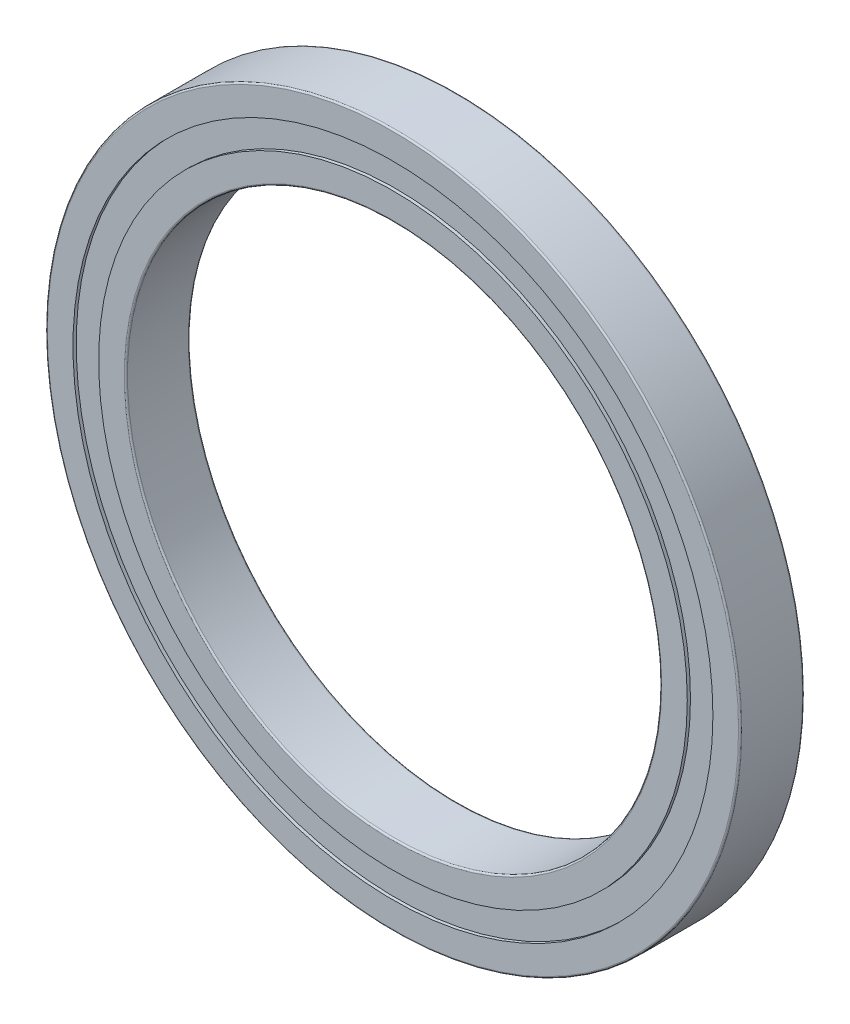
SolidWorks part; units mm, degrees
ref_plane "Front Plane" through (0, 0, 0) normal (0, 0, 1) x (1, 0, 0)
ref_plane "Top Plane" through (0, 0, 0) normal (0, 1, 0) x (1, 0, 0)
ref_plane "Right Plane" through (0, 0, 0) normal (1, 0, 0) x (0, 0, -1)
sketch "Sketch1" plane through (0, 0, 0) normal (0, 0, 1) x (1, 0, 0)
  circle A0 centre (0, 0) radius 25
  circle A1 centre (0, 0) radius 32.5
  dimension "D1" = 50
  dimension "D2" = 65
extrude "Boss-Extrude1" add sketch "Sketch1" along normal blind 6
sketch "Sketch2" plane through (0, 0, 6) normal (0, 0, 1) x (1, 0, 0)
  circle A3 centre (0, 0) radius 29.95
  circle A6 centre (0, 0) radius 27.55
  dimension "D1" = 55.1
  dimension "D2" = 59.9
extrude "Cut-Extrude1" cut sketch "Sketch2" against normal blind 0.3
extrude "Cut-Extrude2" cut sketch "Sketch2<2>" along normal blind 0.5 from surface starting at face at (32.5, 0, 0)
sketch "Sketch2<2>" plane through (0, 0, 6) normal (0, 0, 1) x (1, 0, 0) same geometry as "Sketch2"
fillet "Fillet1" radius 0.15 4 edges at (25, 0, 6) (32.5, 0, 6) (25, 0, 0) (32.5, 0, 0)
